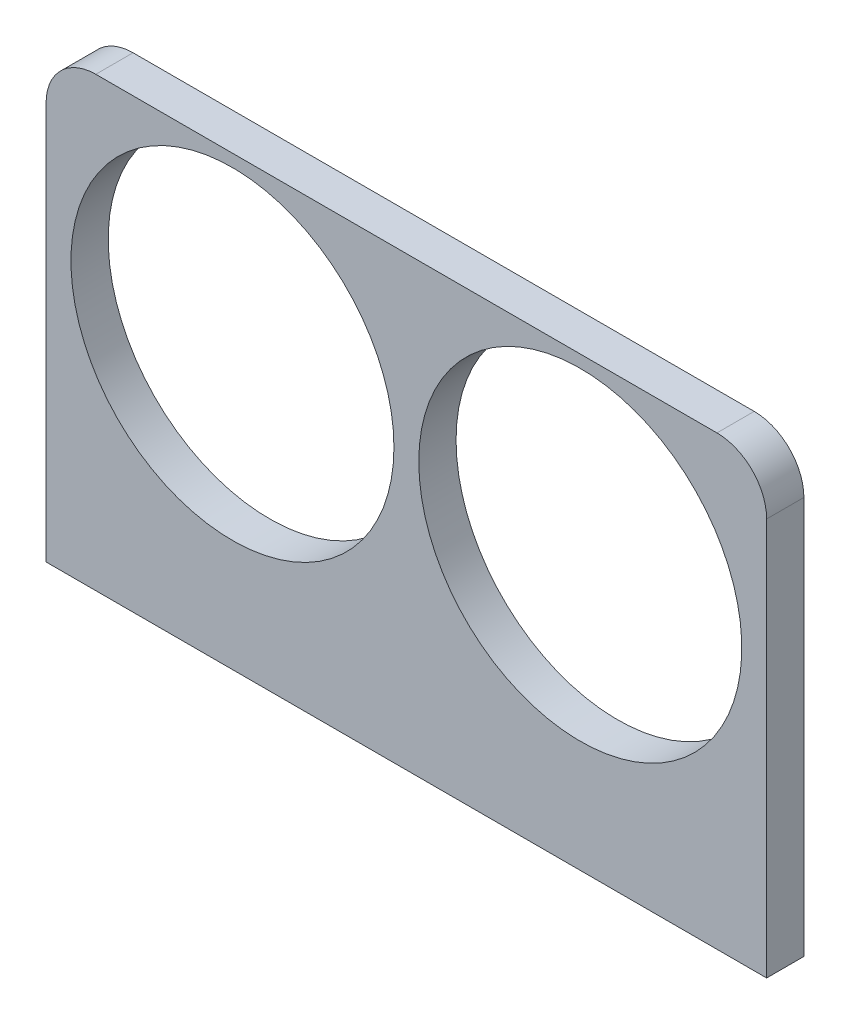
SolidWorks part; units mm, degrees
ref_plane "Front Plane" through (0, 0, 0) normal (0, 0, 1) x (1, 0, 0)
ref_plane "Top Plane" through (0, 0, 0) normal (0, 1, 0) x (1, 0, 0)
ref_plane "Right Plane" through (0, 0, 0) normal (1, 0, 0) x (0, 0, -1)
sketch "Sketch1" plane through (0, 0, 0) normal (0, 0, 1) x (1, 0, 0)
  line L0 (14.5, 18) -> (14.5, -5.1613) construction
  line L1 (0, 0) -> (29, 0)
  line L2 (0, 0) -> (0, 18)
  line L3 (0, 18) -> (29, 18)
  line L4 (29, 0) -> (29, 18)
  line L5 (0, 0) -> (29, 18) construction
  line L6 (0, 18) -> (29, 0) construction
  line L7 (0, 11) -> (29, 11) construction
  circle A0 centre (7.5, 11) radius 6.5
  circle A1 centre (21.5, 11) radius 6.5
  point P4 (14.5, 9)
  dimension "D1" = 13
  dimension "D2" = 7
  dimension "D3" = 7
  dimension "D4" = 29
  dimension "D5" = 18
extrude "Boss-Extrude1" add sketch "Sketch1" along normal blind 1.5
fillet "Fillet1" radius 2 2 edges at (29, 18, 0.75) (0, 18, 0.75)
